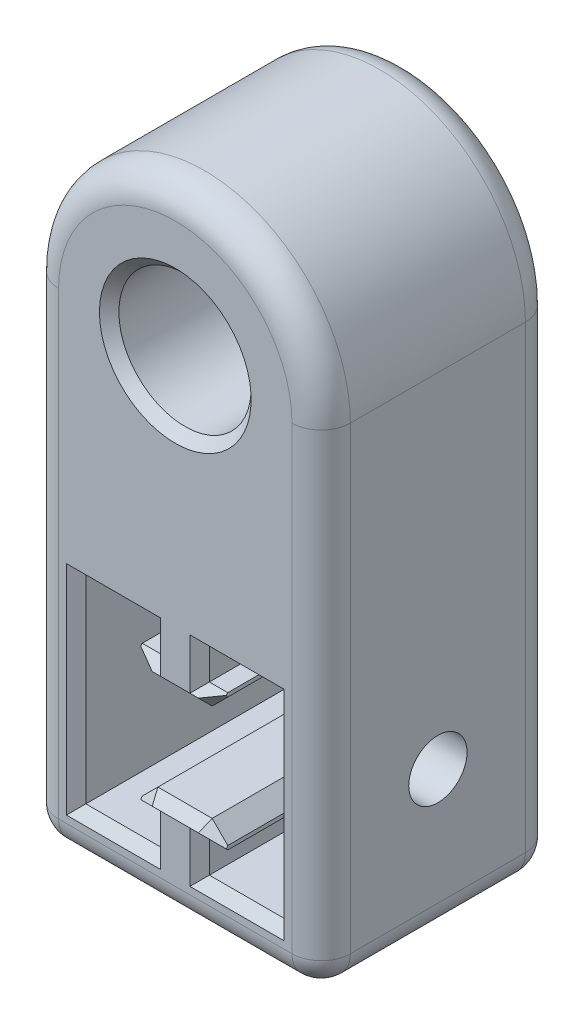
SolidWorks part; units mm, degrees
ref_plane "Front Plane" through (0, 0, 0) normal (0, 0, 1) x (1, 0, 0)
ref_plane "Top Plane" through (0, 0, 0) normal (0, 1, 0) x (1, 0, 0)
ref_plane "Right Plane" through (0, 0, 0) normal (1, 0, 0) x (0, 0, -1)
sketch "Sketch1" plane through (0, 0, 0) normal (0, 0, 1) x (1, 0, 0)
  line L0 (0, -15) -> (0, 15) construction
  line L1 (0, 15) -> (15, 15)
  line L2 (15, 15) -> (15, -14.9496)
  line L3 (15, -14.9496) -> (-15, -14.9496)
  line L4 (-15, -14.9496) -> (-15, 15)
  line L5 (-15, 15) -> (0, 15)
  line L6 (0, -10.2) -> (0, 10.2) construction
  line L7 (0, 10.2) -> (-10.2, 10.2) construction
  line L8 (-10.2, 10.2) -> (-2.5, 10.2)
  line L9 (-2.5, 10.2) -> (-2.5, 7)
  line L10 (-2.5, 7) -> (0, 7) construction
  line L11 (-2.5, 7) -> (-4.4, 7)
  line L12 (-4.4, 7) -> (-4.4, 6.61)
  line L13 (-4.4, 6.61) -> (-2.79, 5)
  line L14 (-2.79, 5) -> (0, 5) construction
  line L15 (-2.79, 5) -> (2.79, 5)
  line L16 (-10.2, 3.1) -> (-10.2, -3.1)
  line L22 (-10.2, 10.2) -> (-10.2, 3.1)
  line L23 (0, 0) -> (-11.0308, 0) construction
  line L24 (4.4, 6.61) -> (2.79, 5)
  line L25 (4.4, 7) -> (4.4, 6.61)
  line L26 (2.5, 7) -> (4.4, 7)
  line L27 (2.5, 10.2) -> (2.5, 7)
  line L28 (10.2, 10.2) -> (2.5, 10.2)
  line L29 (10.2, 10.2) -> (10.2, 3.1)
  line L35 (10.2, 3.1) -> (10.2, -3.1)
  line L36 (-2.79, -5) -> (0, -5) construction
  line L37 (-2.5, -7) -> (0, -7) construction
  line L38 (0, -10.2) -> (-10.2, -10.2) construction
  line L43 (10.2, -10.2) -> (10.2, -3.1)
  line L44 (10.2, -10.2) -> (2.5, -10.2)
  line L45 (2.5, -10.2) -> (2.5, -7)
  line L46 (2.5, -7) -> (4.4, -7)
  line L47 (4.4, -7) -> (4.4, -6.61)
  line L48 (4.4, -6.61) -> (2.79, -5)
  line L49 (-10.2, -10.2) -> (-10.2, -3.1)
  line L54 (-2.79, -5) -> (2.79, -5)
  line L55 (-4.4, -6.61) -> (-2.79, -5)
  line L56 (-4.4, -7) -> (-4.4, -6.61)
  line L57 (-2.5, -7) -> (-4.4, -7)
  line L58 (-2.5, -10.2) -> (-2.5, -7)
  line L59 (-10.2, -10.2) -> (-2.5, -10.2)
  point P43 (4.191, 0)
  point P58 (-4.191, 0)
  dimension "D1" = 2.5
  dimension "D2" = 2.79
  dimension "D3" = 1.9
  dimension "D4" = 135
  dimension "D5" = 2
  dimension "D6" = 15
  dimension "D7" = 15
  dimension "D8" = 10.2
  dimension "D9" = 10.2
  dimension "D10" = 90
  dimension "D11" = 3.2
  dimension "D12" = 15
extrude "Boss-Extrude1" add sketch "Sketch1" along normal blind 24
sketch "Sketch4" plane through (0, 0, 0) normal (0, 0, -1) x (-1, 0, 0)
  line L0 (0, 15) -> (0, 28.5) construction
  line L1 (-15, 15) -> (15, 15) construction
  line L2 (0, 28.5) -> (0, 35.3) construction
  line L3 (-15, 15) -> (-15, 35.3)
  line L4 (15, 35.3) -> (15, 15)
  line L5 (15, 15) -> (-15, 15)
  line L6 (15, -14.9496) -> (-15, -14.9496) construction
  circle A0 centre (0, 35.3) radius 6.8
  arc A1 (-15, 35.3) -> (15, 35.3) centre (0, 35.3) cw
  line M2 (15, 15) -> (-15, 15)
  dimension "D2" = 13.6
  dimension "D3" = 15
  dimension "D1" = 29.9496
  dimension "D4" = 13.5
extrude "Boss-Extrude2" add sketch "Sketch4" against normal up to surface (24 mm away) contours A1 L3 L4 A0 M2
sketch "Sketch3" plane through (-15, 0, 0) normal (-1, 0, 0) x (0, 0, 1)
  line L0 (12, 0) -> (24, 10.1752) construction
  line L2 (0, 0) -> (12, 0) construction
  line L3 (24, 35.3) -> (24, -14.9496) construction
  circle A0 centre (12, 0) radius 3
extrude "Cut-Extrude1" cut sketch "Sketch3" against normal through all
fillet "Fillet1" radius 3 10 edges at (0, -14.9496, 24) (15, 10.1752, 24) (-15, 10.1752, 24) (15, 10.1752, 0) (-15, 10.1752, 0) (0, -14.9496, 0) (15, -14.9496, 12) (-15, -14.9496, 12) (0, 50.3, 24) (0, 50.3, 0)
sketch "Sketch5" plane through (0, 0, 0) normal (0, 0, -1) x (-1, 0, 0)
  line L0 (0, 28.5) -> (0, 42.1) construction
  circle A0 centre (0, 35.3) radius 6.8 construction
  circle A1 centre (0, 35.3) radius 5.5
  circle A2 centre (0, 35.3) radius 6.8
  dimension "D1" = 13.6
extrude "Boss-Extrude3" add sketch "Sketch5" against normal blind 5
chamfer "Chamfer1" distance 1 angle 45 42 edges at (-3.595, 5.805, 0) (0, 5, 0) (3.595, 5.805, 0) (3.45, 7, 0) (2.5, 8.6, 0) (6.35, 10.2, 0) (10.2, 0, 0) (6.35, -10.2, 0) (2.5, -8.6, 0) (3.45, -7, 0) (3.595, -5.805, 0) (0, -5, 0) (-3.595, -5.805, 0) (-3.45, -7, 0) (-2.5, -8.6, 0) (-6.35, -10.2, 0) (-10.2, 0, 0) (-6.35, 10.2, 0) (-2.5, 8.6, 0) (-3.45, 7, 0) (-2.5, 8.6, 24) (-6.35, 10.2, 24) (-10.2, 0, 24) (-6.35, -10.2, 24) (-2.5, -8.6, 24) (-3.45, -7, 24) (-3.595, -5.805, 24) (0, -5, 24) (3.595, -5.805, 24) (3.45, -7, 24) (2.5, -8.6, 24) (6.35, -10.2, 24) (10.2, 0, 24) (6.35, 10.2, 24) (2.5, 8.6, 24) (3.45, 7, 24) (3.595, 5.805, 24) (0, 5, 24) (-3.595, 5.805, 24) (-3.45, 7, 24) (-6.8, 35.3, 24) (-5.5, 35.3, 0)
